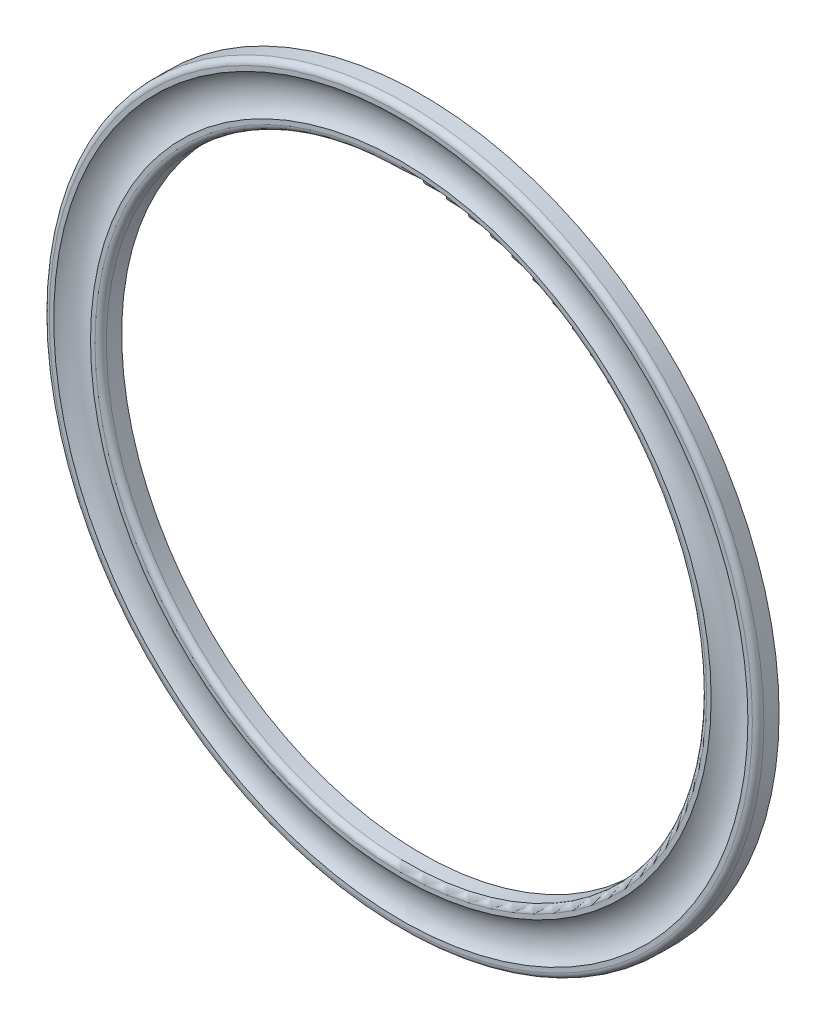
SolidWorks part; units mm, degrees
ref_plane "前基準面" through (0, 0, 0) normal (0, 0, 1) x (1, 0, 0)
ref_plane "上基準面" through (0, 0, 0) normal (0, 1, 0) x (1, 0, 0)
ref_plane "右基準面" through (0, 0, 0) normal (1, 0, 0) x (0, 0, -1)
ref_axis "基準軸1" through (0, -55, 0) along (0, 1, 0)
ref_axis "基準軸2" through (-88.99, 0, 0) along (1, 0, 0)
ref_axis "基準軸3" through (0, 0, 55) along (0, 0, -1)
sketch "草圖3" plane through (0, 0, 0) normal (0, 1, 0) x (1, 0, 0)
  line L1 (-10, 15) -> (10, 15)
  line L2 (0, -55) -> (0, 55) construction
  line L3 (-10, 15) -> (-10, 9.6604)
  line L4 (-8, 7.6604) -> (-6.4279, 7.6604)
  line L5 (10, 15) -> (10, 9.6604)
  line L6 (8, 7.6604) -> (6.4279, 7.6604)
  line L7 (-55, 0) -> (55, 0) construction
  arc A0 (6.4279, 7.6604) -> (-6.4279, 7.6604) centre (0, 0) ccw
  arc A1 (-10, 9.6604) -> (-8, 7.6604) centre (-8, 9.6604) ccw
  arc A2 (10, 9.6604) -> (8, 7.6604) centre (8, 9.6604) cw
  point P8 (0, 15)
  dimension "D2" = 10
  dimension "D5" = 2
  dimension "D6" = 2
  dimension "D1" = 80
  dimension "D3" = 20
  dimension "D4" = 15
  dimension "D7" = 7.3396
ref_plane "平面1" through (115, 0, 0) normal (1, 0, 0) x (0, 0, -1)
ref_axis "基準軸7" through (115, 0, 57.074) along (0, 0, -1)
revolve "旋轉2" add sketch "草圖3" angle 360 about axis through (115, 0, 57.074) along (0, 0, -1)
sketch "草圖4" plane through (0, 0, -15) normal (0, 0, -1) x (-1, 0, 0)
  circle A0 centre (-115, 0) radius 125 construction
  circle A1 centre (-115, 0) radius 125
  circle A2 centre (-115, 0) radius 105 construction
  circle A3 centre (-115, 0) radius 105
  dimension "D1" = 250
  dimension "D2" = 20
